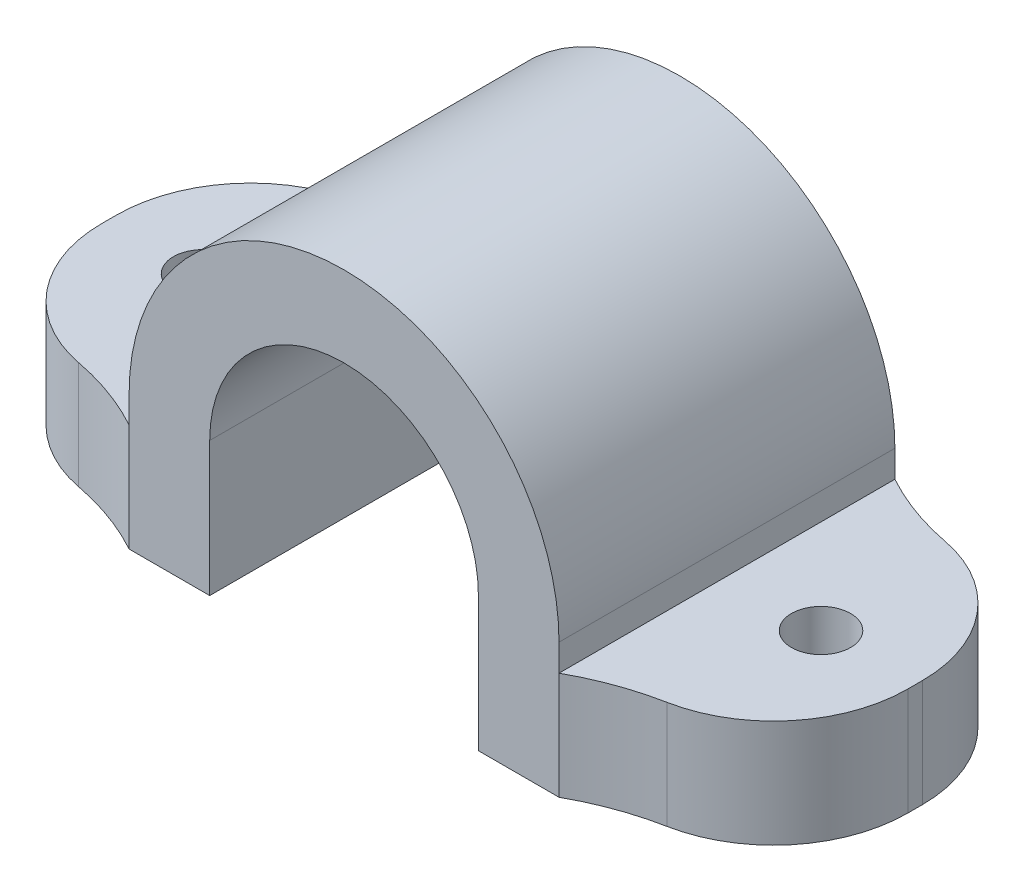
SolidWorks part; units mm, degrees
ref_plane "Front Plane" through (0, 0, 0) normal (0, 0, 1) x (1, 0, 0)
ref_plane "Top Plane" through (0, 0, 0) normal (0, 1, 0) x (1, 0, 0)
ref_plane "Right Plane" through (0, 0, 0) normal (1, 0, 0) x (0, 0, -1)
sketch "Sketch1" plane through (0, 0, 0) normal (0, 0, 1) x (1, 0, 0)
  line L0 (5, 5) -> (5, 0)
  line L1 (-5, 5) -> (-5, 0)
  line L2 (0, 11.4) -> (0, 0) construction
  line L3 (8, 5) -> (8, 0)
  line L4 (-8, 5) -> (-8, 0)
  line L5 (-8, 0) -> (-5, 0)
  line L6 (5, 0) -> (8, 0)
  arc A0 (5, 5) -> (-5, 5) centre (0, 5) ccw
  arc A1 (8, 5) -> (-8, 5) centre (0, 5) ccw
  dimension "D1" = 10
  dimension "D4" = 5
  dimension "D2" = 5
  dimension "D3" = 5
  dimension "D5" = 5
  dimension "D6" = 11.4
  dimension "D7" = 3
extrude "Boss-Extrude1" add sketch "Sketch1" along normal mid plane 12.5
ref_plane "Plane3" through (-15, 0, 0) normal (1, 0, 0) x (0, 0, -1)
sketch "Sketch5" plane through (-15, 0, 0) normal (1, 0, 0) x (0, 0, -1)
  line L1 (-5, 4) -> (5, 4)
  line L2 (-5, 4) -> (-5, 0)
  line L3 (-5, 0) -> (5, 0)
  line L4 (5, 4) -> (5, 0)
  dimension "D1" = 4
  dimension "D2" = 10
extrude "Boss-Extrude4" add sketch "Sketch5" along normal up to next
fillet "Fillet1" radius 10 2 edges at (-8, 2, -5) (-8, 2, 5)
fillet "Fillet2" radius 5 2 edges at (-15, 2, -5) (-15, 2, 5)
sketch "Sketch7" plane through (0, 4, 0) normal (0, 1, 0) x (1, 0, 0)
  line L0 (-8, 0) -> (-15, 0) construction
  line L1 (-8, 6.25) -> (-8, -6.25) construction
  line L2 (-15, 0.2715) -> (-15, -0.2715) construction
  circle A0 centre (-11.5, 0) radius 1.1
  dimension "D1" = 2.2
extrude "Cut-Extrude2" cut sketch "Sketch7" against normal through all
mirror "Mirror6" about plane through (0, 0, 0) normal (1, 0, 0) of "Boss-Extrude4"
mirror "Mirror7" about plane through (0, 0, 0) normal (1, 0, 0) of "Cut-Extrude2"
fillet "Fillet6" radius 10 2 edges at (8, 2, 5) (8, 2, -5)
fillet "Fillet7" radius 5 2 edges at (15, 2, 5) (15, 2, -5)
